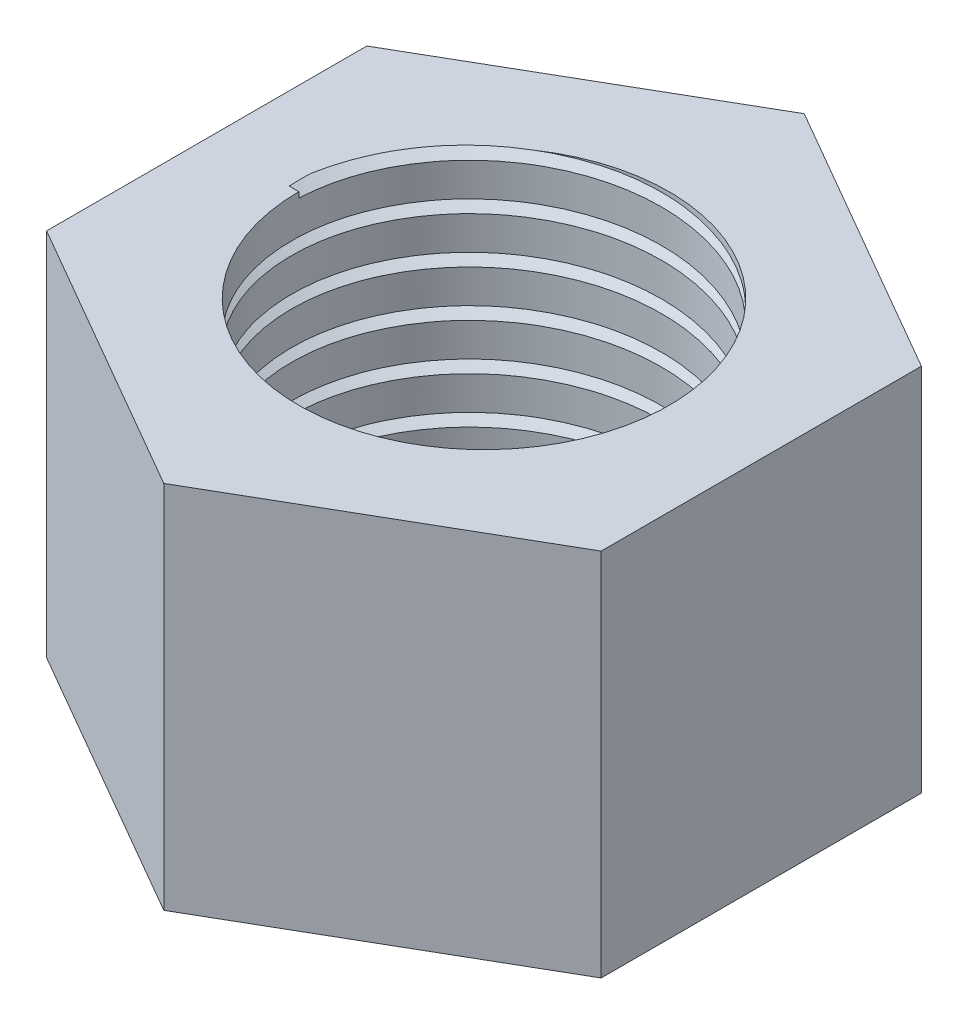
SolidWorks part; units mm, degrees
ref_plane "Front Plane" through (0, 0, 0) normal (0, 0, 1) x (1, 0, 0)
ref_plane "Top Plane" through (0, 0, 0) normal (0, 1, 0) x (1, 0, 0)
ref_plane "Right Plane" through (0, 0, 0) normal (1, 0, 0) x (0, 0, -1)
sketch "Sketch2" plane through (0, 0, 0) normal (0, 1, 0) x (1, 0, 0)
  line L1 (12, 6.9282) -> (0, 13.8564)
  line L2 (0, 13.8564) -> (-12, 6.9282)
  line L3 (-12, 6.9282) -> (-12, -6.9282)
  line L4 (-12, -6.9282) -> (0, -13.8564)
  line L5 (0, -13.8564) -> (12, -6.9282)
  line L6 (12, -6.9282) -> (12, 6.9282)
  circle A0 centre (0, 0) radius 12 construction
  dimension "D1" = 24
extrude "Boss-Extrude1" add sketch "Sketch2" along normal blind 16
sketch "Sketch3" plane through (0, 16, 0) normal (0, 1, 0) x (1, 0, 0)
  circle A0 centre (0, 0) radius 8.0115
  dimension "D1" = 16.023
extrude "Cut-Extrude1" cut sketch "Sketch3" against normal blind 62
sketch "Sketch6" plane through (0, 16, 0) normal (0, 1, 0) x (1, 0, 0)
  circle A0 centre (0, 0) radius 8.0115 construction
  circle A1 centre (0, 0) radius 8.0115
curve "Helix/Spiral2" pitch 2 height 16 turns 8
sketch "Sketch7" plane through (0, 0, 0) normal (0, 0, 1) x (1, 0, 0)
  line L1 (8.489, 15.0346) -> (7.7013, 15.4894)
  line L2 (7.7013, 15.4894) -> (7.7013, 14.5798)
  line L3 (7.7013, 14.5798) -> (8.489, 15.0346)
  circle A0 centre (7.9638, 15.0346) radius 0.2626 construction
  spline S0 degree 3 poles (-8.0115, 16) (-8.0115, 15.9586) (-7.5944, 15.8749) (-5.8125, 15.75) (-3.1457, 15.625) (0, 15.5) (3.1457, 15.375) (5.8125, 15.25) (7.5944, 15.125) (8.2201, 15) (7.5944, 14.875) (5.8125, 14.75) (3.1457, 14.625) (0, 14.5) (-3.1457, 14.375) (-5.8125, 14.25) (-7.5944, 14.125) (-8.2201, 14) (-7.5944, 13.875) (-5.8125, 13.75) (-3.1457, 13.625) (0, 13.5) (3.1457, 13.375) (5.8125, 13.25) (7.5944, 13.125) (8.2201, 13) (7.5944, 12.875) (5.8125, 12.75) (3.1457, 12.625) (0, 12.5) (-3.1457, 12.375) (-5.8125, 12.25) (-7.5944, 12.125) (-8.2201, 12) (-7.5944, 11.875) (-5.8125, 11.75) (-3.1457, 11.625) (0, 11.5) (3.1457, 11.375) (5.8125, 11.25) (7.5944, 11.125) (8.2201, 11) (7.5944, 10.875) (5.8125, 10.75) (3.1457, 10.625) (0, 10.5) (-3.1457, 10.375) (-5.8125, 10.25) (-7.5944, 10.125) (-8.2201, 10) (-7.5944, 9.875) (-5.8125, 9.75) (-3.1457, 9.625) (0, 9.5) (3.1457, 9.375) (5.8125, 9.25) (7.5944, 9.125) (8.2201, 9) (7.5944, 8.875) (5.8125, 8.75) (3.1457, 8.625) (0, 8.5) (-3.1457, 8.375) (-5.8125, 8.25) (-7.5944, 8.125) (-8.2201, 8) (-7.5944, 7.875) (-5.8125, 7.75) (-3.1457, 7.625) (0, 7.5) (3.1457, 7.375) (5.8125, 7.25) (7.5944, 7.125) (8.2201, 7) (7.5944, 6.875) (5.8125, 6.75) (3.1457, 6.625) (0, 6.5) (-3.1457, 6.375) (-5.8125, 6.25) (-7.5944, 6.125) (-8.2201, 6) (-7.5944, 5.875) (-5.8125, 5.75) (-3.1457, 5.625) (0, 5.5) (3.1457, 5.375) (5.8125, 5.25) (7.5944, 5.125) (8.2201, 5) (7.5944, 4.875) (5.8125, 4.75) (3.1457, 4.625) (0, 4.5) (-3.1457, 4.375) (-5.8125, 4.25) (-7.5944, 4.125) (-8.2201, 4) (-7.5944, 3.875) (-5.8125, 3.75) (-3.1457, 3.625) (0, 3.5) (3.1457, 3.375) (5.8125, 3.25) (7.5944, 3.125) (8.2201, 3) (7.5944, 2.875) (5.8125, 2.75) (3.1457, 2.625) (0, 2.5) (-3.1457, 2.375) (-5.8125, 2.25) (-7.5944, 2.125) (-8.2201, 2) (-7.5944, 1.875) (-5.8125, 1.75) (-3.1457, 1.625) (0, 1.5) (3.1457, 1.375) (5.8125, 1.25) (7.5944, 1.125) (8.2201, 1) (7.5944, 0.875) (5.8125, 0.75) (3.1457, 0.625) (0, 0.5) (-3.1457, 0.375) (-5.8125, 0.25) (-7.5944, 0.1251) (-8.0115, 0.0414) (-8.0115, 0) knots 0 0 0 0 0.007812 0.015625 0.023437 0.03125 0.039062 0.046875 0.054687 0.0625 0.070312 0.078125 0.085937 0.09375 0.101562 0.109375 0.117187 0.125 0.132812 0.140625 0.148437 0.15625 0.164062 0.171875 0.179687 0.1875 0.195312 0.203125 0.210937 0.21875 0.226562 0.234375 0.242187 0.25 0.257812 0.265625 0.273437 0.28125 0.289062 0.296875 0.304687 0.3125 0.320312 0.328125 0.335937 0.34375 0.351562 0.359375 0.367187 0.375 0.382812 0.390625 0.398437 0.40625 0.414062 0.421875 0.429687 0.4375 0.445312 0.453125 0.460937 0.46875 0.476562 0.484375 0.492187 0.5 0.507812 0.515625 0.523437 0.53125 0.539062 0.546875 0.554687 0.5625 0.570312 0.578125 0.585937 0.59375 0.601562 0.609375 0.617187 0.625 0.632812 0.640625 0.648437 0.65625 0.664062 0.671875 0.679687 0.6875 0.695312 0.703125 0.710937 0.71875 0.726562 0.734375 0.742187 0.75 0.757812 0.765625 0.773437 0.78125 0.789062 0.796875 0.804688 0.8125 0.820312 0.828125 0.835938 0.84375 0.851562 0.859375 0.867188 0.875 0.882812 0.890625 0.898438 0.90625 0.914062 0.921875 0.929688 0.9375 0.945312 0.953125 0.960938 0.96875 0.976562 0.984375 0.992188 1 1 1 1 construction
sweep "Cut-Sweep2" cut profiles "Sketch7" path "Helix/Spiral2"
